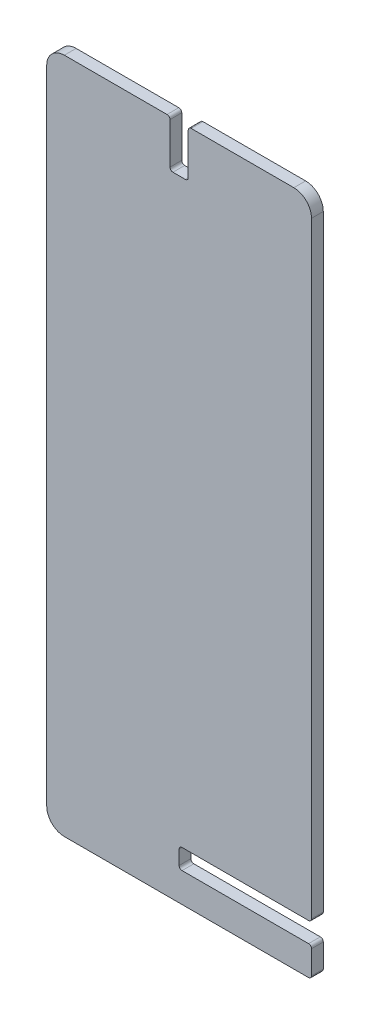
SolidWorks part; units mm, degrees
ref_plane "Alzado" through (0, 0, 0) normal (0, 0, 1) x (1, 0, 0)
ref_plane "Planta" through (0, 0, 0) normal (0, 1, 0) x (1, 0, 0)
ref_plane "Vista lateral" through (0, 0, 0) normal (1, 0, 0) x (0, 0, -1)
sketch "Croquis1" plane through (0, 0, 0) normal (0, 0, 1) x (1, 0, 0)
  line L1 (-22.5, 45) -> (22.5, 45)
  line L2 (-22.5, 45) -> (-22.5, -70)
  line L3 (-22.5, -70) -> (22.5, -70)
  line L4 (22.5, 45) -> (22.5, -70)
  dimension "D1" = 45
  dimension "D2" = 22.5
  dimension "D3" = 115
  dimension "D4" = 45
extrude "Saliente-Extruir1" add sketch "Croquis1" along normal blind 2 contours L2 L3 L4 L1
sketch "Croquis3" plane through (0, 0, 2) normal (0, 0, 1) x (1, 0, 0)
  line L0 (22.5, 45) -> (22.5, -70) construction
  line L1 (22.5, -61.6) -> (0, -61.6)
  line L2 (22.5, -61.6) -> (22.5, -65)
  line L3 (22.5, -65) -> (0, -65)
  line L4 (0, -61.6) -> (0, -65)
  line L5 (-22.5, -70) -> (22.5, -70) construction
  dimension "D1" = 3.4
  dimension "D2" = 5
  dimension "D3" = 22.5
extrude "Cortar-Extruir2" cut sketch "Croquis3" against normal up to surface (2 mm away) up to face at (0, -12.5, 0)
fillet "Redondeo1" radius 3 3 edges at (-22.5, -70, 1) (22.5, 45, 1) (-22.5, 45, 1)
sketch "Croquis4" plane through (0, 0, 2) normal (0, 0, 1) x (1, 0, 0)
  line L5 (0, 0) -> (0, 53.685) construction
  line L6 (-19.5, 45) -> (19.5, 45) construction
  line L7 (-1.55, 45) -> (1.55, 45)
  line L8 (-1.55, 45) -> (-1.55, 37)
  line L9 (-1.55, 37) -> (1.55, 37)
  line L10 (1.55, 45) -> (1.55, 37)
  dimension "D1" = 1.55
  dimension "D2" = 1.55
  dimension "D3" = 8
extrude "Cortar-Extruir3" cut sketch "Croquis4" against normal up to surface (2 mm away) up to face at (2.2617, -25.9617, 0)
fillet "Redondeo2" radius 0.5 9 edges at (0, -61.6, 1) (0, -65, 1) (22.5, -70, 1) (22.5, -65, 1) (22.5, -61.6, 1) (-1.55, 37, 1) (1.55, 37, 1) (-1.55, 45, 1) (1.55, 45, 1)
